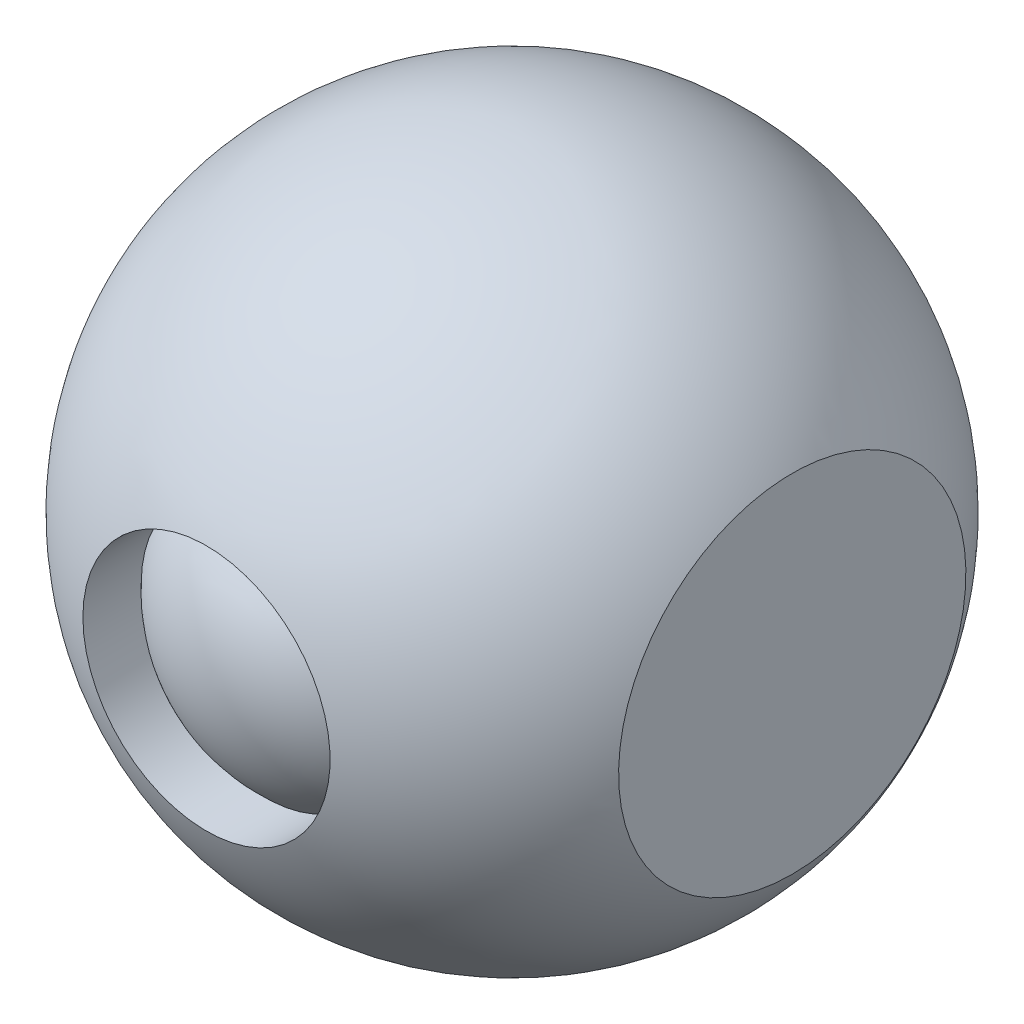
SolidWorks part; units mm, degrees
ref_plane "前视基准面" through (0, 0, 0) normal (0, 0, 1) x (1, 0, 0)
ref_plane "上视基准面" through (0, 0, 0) normal (0, 1, 0) x (1, 0, 0)
ref_plane "右视基准面" through (0, 0, 0) normal (1, 0, 0) x (0, 0, -1)
sketch "草图1" plane through (0, 0, 0) normal (0, 0, 1) x (1, 0, 0)
  line L0 (-51, 0) -> (51, 0)
  line L1 (51, 0) -> (51, 31.607)
  line L2 (0, 0) -> (0, -88.576) construction
  line L3 (-51, 0) -> (-51, 31.607)
  arc A1 (51, 31.607) -> (-51, 31.607) centre (0, 0) ccw
  dimension "D1" = 60
  dimension "D2" = 51
revolve "旋转1" add sketch "草图1" angle 360 about L0
sketch "草图3" plane through (0, 0, 0) normal (0, 0, 1) x (1, 0, 0)
  circle A0 centre (0, 0) radius 22.5
  dimension "D1" = 45
extrude "切除-拉伸1" cut sketch "草图3" along normal up to surface (55.6215 mm away) up to face at (-51, -31.607, 0)
sketch "草图4" plane through (0, 0, 0) normal (0, 0, 1) x (1, 0, 0)
  circle A1 centre (0, 0) radius 22.5
  circle A2 centre (0, 0) radius 22.5
  dimension "D1" = 0
extrude "凸台-拉伸1" add sketch "草图4" along normal blind 45
dome "圆顶1" faces to dome 1 distance 10 reverse direction no elliptical dome no face at (22.5, 0, 45) parameters "D1"=10
